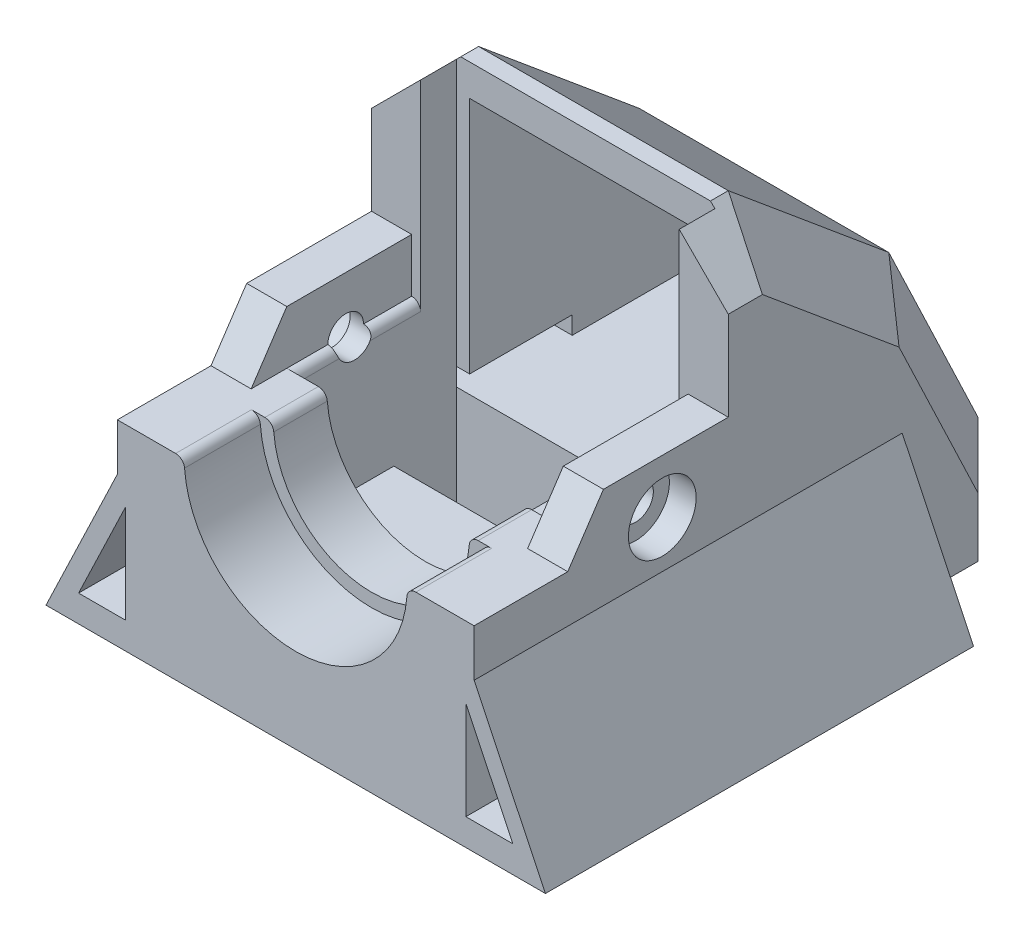
SolidWorks part; units mm, degrees
ref_plane "Ebene vorne" through (0, 0, 0) normal (0, 0, 1) x (1, 0, 0)
ref_plane "Ebene oben" through (0, 0, 0) normal (0, 1, 0) x (1, 0, 0)
ref_plane "Ebene rechts" through (0, 0, 0) normal (1, 0, 0) x (0, 0, -1)
sketch "Skizze1" plane through (0, 0, 0) normal (0, 0, 1) x (1, 0, 0)
  line L1 (0, 0) -> (20, 0)
  line L2 (0, 0) -> (0, 22)
  line L3 (0, 22) -> (20, 22)
  line L4 (20, 0) -> (20, 22)
  dimension "D1" = 22
  dimension "D2" = 20
extrude "Aufsatz-Linear austragen1" add sketch "Skizze1" along normal blind 35
sketch "Skizze2" plane through (0, 0, 35) normal (0, 0, 1) x (1, 0, 0)
  line L0 (0, 22) -> (0, 0) construction
  line L1 (20, 22) -> (0, 22) construction
  circle A0 centre (10, 11) radius 5.5
  dimension "D3" = 11
  dimension "D1" = 10
  dimension "D2" = 11
extrude "Schnitt-Linear austragen1" cut sketch "Skizze2" against normal blind 11
sketch "Skizze3" plane through (0, 0, 35) normal (0, 0, 1) x (1, 0, 0)
  line L0 (20, 0) -> (20, 22) construction
  line L1 (20, 22) -> (0, 22) construction
  circle A0 centre (10, 11) radius 6.25
  dimension "D1" = 10
  dimension "D2" = 11
extrude "Schnitt-Linear austragen2" cut sketch "Skizze3" against normal blind 8
sketch "Skizze5" plane through (0, 0, 24) normal (0, 0, 1) x (1, 0, 0)
  line L0 (0, 22) -> (0, 0) construction
  line L1 (2.75, 3.75) -> (17.25, 3.75)
  line L2 (2.75, 3.75) -> (2.75, 22)
  line L3 (2.75, 22) -> (17.25, 22)
  line L4 (17.25, 3.75) -> (17.25, 22)
  line L6 (0, 0) -> (20, 0) construction
  dimension "D1" = 18.25
  dimension "D2" = 14.5
  dimension "D3" = 2.75
  dimension "D4" = 3.75
extrude "Schnitt-Linear austragen3" cut sketch "Skizze5" against normal blind 9
sketch "Skizze13" plane through (0, 0, 35) normal (0, 0, 1) x (1, 0, 0)
  line L0 (20, 0) -> (20, 22) construction
  line L1 (0, 22) -> (20, 22)
  line L2 (0, 22) -> (0, 11)
  line L3 (0, 11) -> (20, 11)
  line L4 (20, 22) -> (20, 11)
extrude "Schnitt-Linear austragen6" cut sketch "Skizze13" against normal blind 18
sketch "Skizze16" plane through (0, 0, 0) normal (-1, 0, 0) x (0, 0, 1)
  line L0 (14, 22) -> (5, 14.5)
  line L1 (17, 22) -> (0, 22) construction
  line L2 (5, 14.5) -> (0, 4)
  line L3 (0, 22) -> (0, 0) construction
  line L4 (0, 4) -> (0, 22)
  line L5 (0, 22) -> (14, 22)
  line L6 (17, 22) -> (17, 11) construction
  dimension "D1" = 3
  dimension "D2" = 5
  dimension "D3" = 18
  dimension "D4" = 10.5
extrude "Schnitt-Linear austragen7" cut sketch "Skizze16" against normal through all
fillet "Verrundung1" radius 0.5 6 edges at (16.25, 11, 31) (3.75, 11, 31) (4.5, 11, 25.5) (15.5, 11, 25.5) (17.25, 11, 20.5) (2.75, 11, 20.5)
chamfer "Fase1" distance 3 angle 45 2 edges at (20, 22, 15.5) (0, 22, 15.5)
chamfer "Fase2" distance 3 angle 45 2 edges at (0, 16.75, 7.7) (20, 16.75, 7.7)
chamfer "Fase3" distance 3 angle 45 4 edges at (20, 6.0129, 0.9585) (20, 2, 0) (0, 6.0129, 0.9585) (0, 2, 0)
chamfer "Fase4" distance 1.5 angle 45 2 edges at (20, 11, 26) (0, 11, 26)
sketch "Skizze17" plane through (0, 3.75, 0) normal (0, 1, 0) x (1, 0, 0)
  line L1 (2.75, -15) -> (8.75, -15)
  line L2 (2.75, -15) -> (2.75, -18.5)
  line L3 (2.75, -18.5) -> (8.75, -18.5)
  line L4 (8.75, -15) -> (8.75, -18.5)
  dimension "D1" = 6
  dimension "D2" = 3.5
extrude "Schnitt-Linear austragen8" cut sketch "Skizze17" against normal through all
sketch "Skizze18" plane through (0, 0, 0) normal (-1, 0, 0) x (0, 0, 1)
  line L0 (17, 11) -> (35, 11) construction
  line L1 (35, 0) -> (31.25, 0)
  line L2 (35, 0) -> (35, 11)
  line L3 (35, 11) -> (31.25, 11)
  line L4 (31.25, 0) -> (31.25, 11)
  dimension "D1" = 3.75
extrude "Schnitt-Linear austragen9" cut sketch "Skizze18" against normal up to surface (20 mm away) up to face at (20, 9.1173, 16.564)
ref_plane "Ebene1" through (10, 0, 0) normal (-1, 0, 0) x (0, 0, 1)
sketch "Skizze22" plane through (10, 0, 0) normal (-1, 0, 0) x (0, 0, 1)
  line L0 (15, 20.2299) -> (6.6172, 13.2443)
  line L1 (15, 3.75) -> (15, 21.75) construction
  line L2 (7.4258, 12.6164) -> (5, 14.5) construction
  line L3 (6.6172, 13.2443) -> (5.76, 11.8961)
  line L4 (5.76, 11.8961) -> (3.76, 11.8961)
  line L5 (5, 14.5) -> (0, 4) construction
  line L6 (3.76, 11.8961) -> (0.8806, 5.8493)
  line L7 (0.8806, 5.8493) -> (6.0352, 5.8493)
  line L8 (6.0352, 5.8493) -> (15, 5.8493)
  line L9 (15, 5.8493) -> (15, 20.2299)
  line L10 (14, 22) -> (5, 14.5) construction
  dimension "D1" = 2
  dimension "D2" = 2
extrude "Schnitt-Linear austragen10" cut sketch "Skizze22" against normal blind 6.5 and the other way blind 6.5
sketch "Skizze23" plane through (0, 0, 31.25) normal (0, 0, 1) x (1, 0, 0)
  line L0 (0, 8.353) -> (-4, 0)
  line L1 (-4, 0) -> (0, 0)
  line L2 (0, 0) -> (0, 8.353)
  point P3 (0, 8.353)
  dimension "D1" = 4
extrude "Aufsatz-Linear austragen2" add sketch "Skizze23" against normal blind 24
mirror "Spiegeln1" about plane through (10, 0, 0) normal (-1, 0, 0) of "Aufsatz-Linear austragen2"
sketch "Skizze24" plane through (0, 0, 31.25) normal (0, 0, 1) x (1, 0, 0)
  line L0 (0.4608, 1.5) -> (-2.173, 1.5)
  line L1 (-2.173, 1.5) -> (0.4608, 7)
  line L2 (0.4608, 7) -> (0.4608, 1.5)
  line L3 (0, 8.353) -> (-4, 0) construction
  line L4 (24, 0) -> (-4, 0) construction
  dimension "D1" = 1
  dimension "D2" = 1.5
  dimension "D3" = 5.5
extrude "Schnitt-Linear austragen11" cut sketch "Skizze24" against normal blind 22
sketch "Skizze26" plane through (16.5, 0, 0) normal (-1, 0, 0) x (0, 0, 1)
  line L1 (15, 5.8493) -> (9.25, 5.8493)
  line L2 (15, 5.8493) -> (15, 6.8493)
  line L3 (15, 6.8493) -> (9.25, 6.8493)
  line L4 (9.25, 5.8493) -> (9.25, 6.8493)
  dimension "D1" = 5.75
  dimension "D2" = 1
extrude "Schnitt-Linear austragen12" cut sketch "Skizze26" against normal blind 4
mirror "Spiegeln2" about plane through (10, 0, 0) normal (-1, 0, 0) of "Schnitt-Linear austragen12"
mirror "Spiegeln3" about plane through (10, 0, 0) normal (-1, 0, 0) of "Schnitt-Linear austragen11"
sketch "Skizze27" plane through (0, 0, 17) normal (0, 0, 1) x (1, 0, 0)
  line L0 (0, 9.5) -> (1.5, 11)
  line L1 (1.5, 11) -> (0, 11)
  line L2 (0, 19) -> (0, 9.5) construction
  line L3 (0, 11) -> (0, 9.5)
extrude "Aufsatz-Linear austragen3" add sketch "Skizze27" along normal up to surface (14.25 mm away) up to face at (10, 7.9324, 31.25)
mirror "Spiegeln4" about plane through (10, 0, 0) normal (-1, 0, 0) of "Aufsatz-Linear austragen3"
sketch "Skizze28" plane through (0, 0, 17) normal (0, 0, 1) x (1, 0, 0)
  line L5 (0, 19) -> (0, 11) construction
  line L6 (2.25, 11) -> (0, 11)
  line L7 (2.25, 11) -> (2.25, 14)
  line L8 (2.25, 14) -> (0, 14)
  line L9 (0, 11) -> (0, 14)
  dimension "D1" = 3
extrude "Aufsatz-Linear austragen4" add sketch "Skizze28" along normal up to surface (7 mm away) up to face at (10, 8.8943, 24)
sketch "Skizze31" plane through (0, 0, 0) normal (-1, 0, 0) x (0, 0, 1)
  line L0 (24, 14) -> (26, 11)
  line L1 (31.25, 11) -> (24, 11) construction
  line L2 (26, 11) -> (24, 11)
  line L3 (24, 11) -> (24, 14)
  dimension "D1" = 2
extrude "Aufsatz-Linear austragen6" add sketch "Skizze31" against normal up to surface (2.25 mm away) up to face at (2.25, 12.5, 20.5)
sketch "Skizze32" plane through (0, 0, 0) normal (-1, 0, 0) x (0, 0, 1)
  line L2 (31.25, 11) -> (26, 11) construction
  circle A0 centre (20.7, 11) radius 1
  point P2 (0, 0)
  dimension "D1" = 2
  dimension "D2" = 3.3
extrude "Schnitt-Linear austragen13" cut sketch "Skizze32" against normal up to surface (2.75 mm away) up to face at (2.75, 8.4699, 17.9)
sketch "Skizze33" plane through (10, 0, 0) normal (-1, 0, 0) x (0, 0, 1)
  circle A0 centre (20.7, 11) radius 1.9
  dimension "D1" = 3.8
extrude "Schnitt-Linear austragen14" cut sketch "Skizze33" against normal blind 1.5 from surface starting at face at (0, 11, 21.7)
mirror "Spiegeln6" about plane through (10, 0, 0) normal (-1, 0, 0) of "Aufsatz-Linear austragen6", "Aufsatz-Linear austragen4"
mirror "Spiegeln8" about plane through (10, 0, 0) normal (-1, 0, 0) of "Schnitt-Linear austragen13"
sketch "Skizze34" plane through (20, 0, 0) normal (1, 0, 0) x (0, 0, -1)
  circle A0 centre (-20.7, 11) radius 1.9
  dimension "D1" = 3.8
extrude "Schnitt-Linear austragen15" cut sketch "Skizze34" against normal blind 1.5
